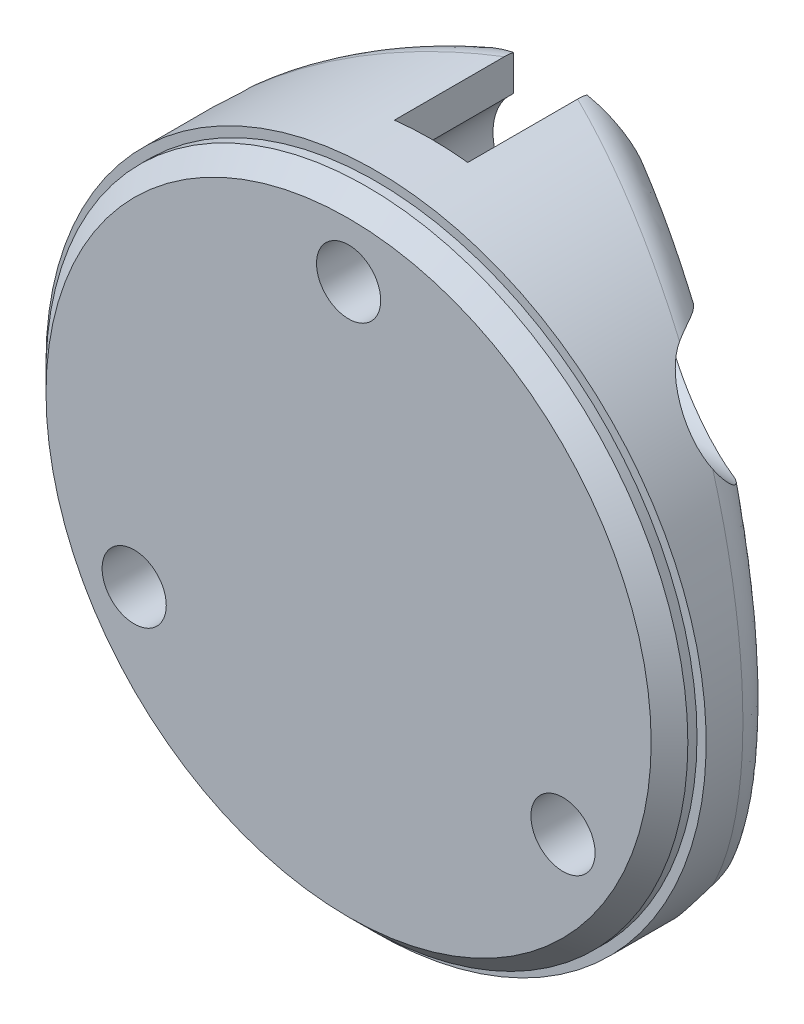
SolidWorks part; units mm, degrees
ref_plane "Front Plane" through (0, 0, 0) normal (0, 0, 1) x (1, 0, 0)
ref_plane "Top Plane" through (0, 0, 0) normal (0, 1, 0) x (1, 0, 0)
ref_plane "Right Plane" through (0, 0, 0) normal (1, 0, 0) x (0, 0, -1)
sketch "Sketch1" plane through (0, 0, 0) normal (0, 0, 1) x (1, 0, 0)
  circle A0 centre (0, 0) radius 17.5
  dimension "D1" = 35
extrude "Boss-Extrude1" add sketch "Sketch1" along normal blind 1.5
sketch "Sketch2" plane through (0, 0, 0) normal (0, 0, -1) x (-1, 0, 0)
  circle A0 centre (0, 0) radius 18
  dimension "D1" = 36
extrude "Boss-Extrude2" add sketch "Sketch2" along normal blind 3
chamfer "Chamfer1" distance 1 angle 45 1 edges at (17.5, 0, 1.5)
sketch "Sketch3" plane through (0, 0, 0) normal (0, 1, 0) x (1, 0, 0)
  line L0 (0, 0) -> (0, 9.5) construction
  line L1 (-18.5, 3) -> (-5.274, 9.5)
  line L2 (-5.274, 9.5) -> (-2, 9.5)
  line L3 (-2, 9.5) -> (-2, 3)
  line L4 (18, 3) -> (-18, 3) construction
  line L5 (-18.5, 3) -> (-2, 3)
  line L6 (18.5, 3) -> (2, 3)
  line L7 (2, 9.5) -> (2, 3)
  line L8 (5.274, 9.5) -> (2, 9.5)
  line L9 (18.5, 3) -> (5.274, 9.5)
  line L10 (18, 3) -> (-18, 3) construction
  dimension "D1" = 4
  dimension "D2" = 6.5
extrude "Boss-Extrude3" add sketch "Sketch3" along normal mid plane 40
sketch "Sketch4" plane through (0, 0, 0) normal (1, 0, 0) x (0, 0, -1)
  line L0 (5.75, 11) -> (5.75, -11) construction
  line L1 (9.5, 20) -> (9.5, -20) construction
  circle A0 centre (5.75, 11) radius 1.5
  circle A1 centre (5.75, -11) radius 1.5
  point P4 (5.75, 0)
  dimension "D1" = 3
  dimension "D2" = 22
  dimension "D3" = 3.75
extrude "Cut-Extrude1" cut sketch "Sketch4" against normal through all both and the other way through all
sketch "Sketch6" plane through (0, 0, 1.5) normal (0, 0, 1) x (1, 0, 0)
  line L1 (23.3622, -22.945) -> (-23.3622, -22.945)
  line L2 (23.3622, -22.945) -> (23.3622, 22.945)
  line L3 (23.3622, 22.945) -> (-23.3622, 22.945)
  line L4 (-23.3622, -22.945) -> (-23.3622, 22.945)
  line L5 (23.3622, -22.945) -> (-23.3622, 22.945) construction
  line L6 (23.3622, 22.945) -> (-23.3622, -22.945) construction
  circle A0 centre (0, 0) radius 18
  arc A1 (2, -17.8885) -> (2, 17.8885) centre (0, 0) ccw construction
extrude "Cut-Extrude2" cut sketch "Sketch6" against normal through all both and the other way through all
sketch "Sketch7" plane through (0, 0, -3) normal (0, 0, -1) x (-1, 0, 0)
  line L0 (2, 17.8885) -> (2, -17.8885) construction
  line L1 (-2, 7) -> (2, 7)
  line L2 (-2, 7) -> (-2, -7)
  line L3 (-2, -7) -> (2, -7)
  line L4 (2, 7) -> (2, -7)
  line L5 (-2, 7) -> (2, -7) construction
  line L6 (-2, -7) -> (2, 7) construction
  point P0 (0, 0)
  dimension "D1" = 14
extrude "Cut-Extrude3" cut sketch "Sketch7" against normal blind 3
sketch "Sketch8" plane through (0, 0, 0) normal (1, 0, 0) x (0, 0, -1)
  circle A0 centre (5.75, 11) radius 2.75
  circle A1 centre (5.75, -11) radius 2.75
  dimension "D1" = 5.5
extrude "Cut-Extrude4" cut sketch "Sketch8" along normal blind 33 from offset 6
sketch "Sketch9" plane through (0, 0, 0) normal (1, 0, 0) x (0, 0, -1)
  line L1 (7.3377, 8.25) -> (8.9254, 11)
  line L2 (8.9254, 11) -> (7.3377, 13.75)
  line L3 (7.3377, 13.75) -> (4.1623, 13.75)
  line L4 (4.1623, 13.75) -> (2.5746, 11)
  line L5 (2.5746, 11) -> (4.1623, 8.25)
  line L6 (4.1623, 8.25) -> (7.3377, 8.25)
  line L7 (4.1623, -13.75) -> (7.3377, -13.75)
  line L8 (7.3377, -13.75) -> (8.9254, -11)
  line L9 (8.9254, -11) -> (7.3377, -8.25)
  line L10 (7.3377, -8.25) -> (4.1623, -8.25)
  line L11 (4.1623, -8.25) -> (2.5746, -11)
  line L12 (2.5746, -11) -> (4.1623, -13.75)
  circle A0 centre (5.75, 11) radius 2.75 construction
  circle A1 centre (5.75, -11) radius 2.75 construction
  dimension "D1" = 5.5
extrude "Cut-Extrude5" cut sketch "Sketch9" against normal blind 33 from offset 5 offset against normal yes
fillet "Fillet1" radius 2 6 edges at (8.6647, 15.7773, -7.8336) (18, 0, -3.2457) (8.6647, -15.7773, -7.8336) (-8.6205, -15.8015, -7.8553) (-8.6205, 15.8015, -7.8553) (-18, 0, -3.2457)
sketch "Sketch10" plane through (0, 0, 1.5) normal (0, 0, 1) x (1, 0, 0)
  line L0 (0, 13.5) -> (11.6913, -6.75) construction
  line L1 (11.6913, -6.75) -> (-11.6913, -6.75) construction
  line L2 (-11.6913, -6.75) -> (0, 13.5) construction
  circle A0 centre (0, 0) radius 13.5 construction
  circle A1 centre (0, 13.5) radius 1.75
  circle A2 centre (11.6913, -6.75) radius 1.75
  circle A3 centre (-11.6913, -6.75) radius 1.75
  point P9 (0, 0)
  point P10 (-13.5, 0)
  point P11 (0, 13.5)
  dimension "D1" = 27
  dimension "D2" = 3.5
extrude "Cut-Extrude6" cut sketch "Sketch10" against normal through all
sketch "Sketch12" plane through (0, 0, -9.5) normal (0, 0, -1) x (-1, 0, 0)
  circle A0 centre (-11.6913, -6.75) radius 3.125
  circle A1 centre (0, 13.5) radius 3.125
  circle A2 centre (11.6913, -6.75) radius 3.125
  dimension "D1" = 6.25
extrude "Cut-Extrude7" cut sketch "Sketch12" against normal blind 6
sketch "Sketch13" plane through (0, 0, 0) normal (1, 0, 0) x (0, 0, -1)
  circle A0 centre (35, 0) radius 28
  dimension "D1" = 56
  dimension "D2" = 35
extrude "Cut-Extrude8" cut sketch "Sketch13" against normal blind 22 from offset 6 offset against normal yes
